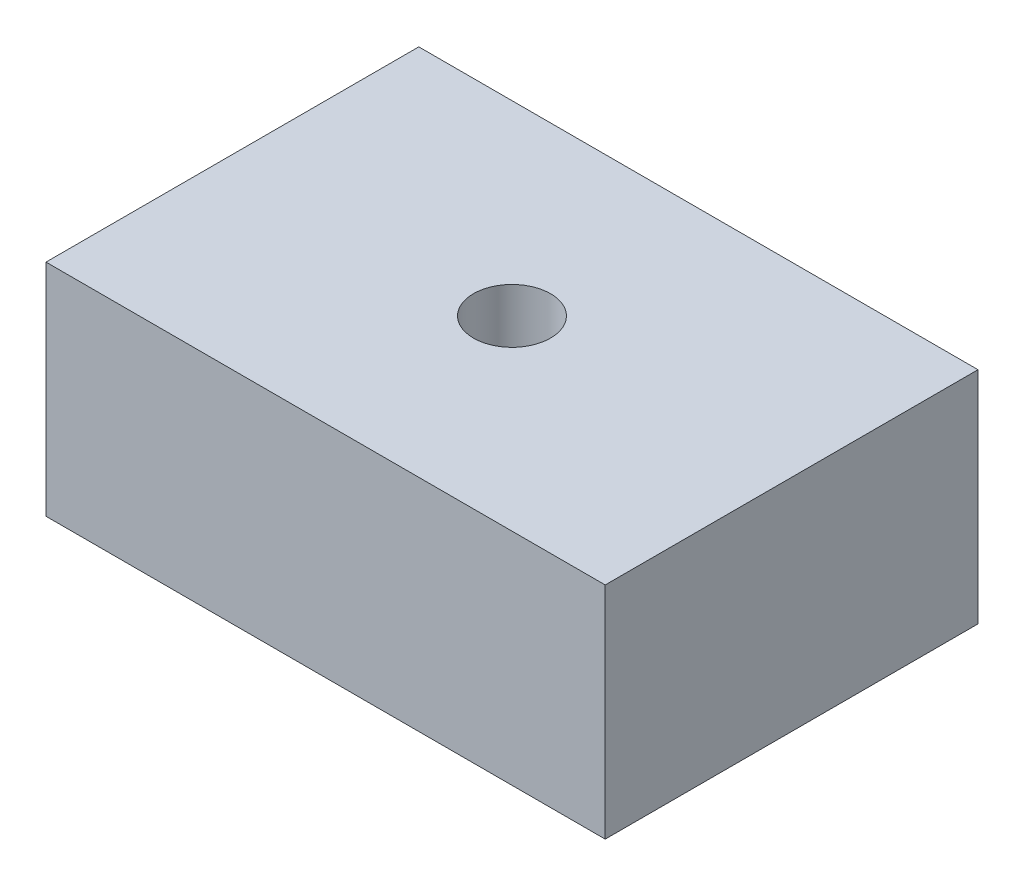
SolidWorks part; units mm, degrees
ref_plane "Front Plane" through (0, 0, 0) normal (0, 0, 1) x (1, 0, 0)
ref_plane "Top Plane" through (0, 0, 0) normal (0, 1, 0) x (1, 0, 0)
ref_plane "Right Plane" through (0, 0, 0) normal (1, 0, 0) x (0, 0, -1)
sketch "Sketch1" plane through (0, 0, 0) normal (0, 1, 0) x (1, 0, 0)
  line L1 (-38.1, 25.4) -> (38.1, 25.4)
  line L2 (-38.1, 25.4) -> (-38.1, -25.4)
  line L3 (-38.1, -25.4) -> (38.1, -25.4)
  line L4 (38.1, 25.4) -> (38.1, -25.4)
  line L5 (-38.1, 25.4) -> (38.1, -25.4) construction
  line L6 (-38.1, -25.4) -> (38.1, 25.4) construction
  circle A0 centre (0, 0) radius 5.25
  dimension "D1" = 50.8
  dimension "D2" = 76.2
extrude "Boss-Extrude1" add sketch "Sketch1" along normal blind 30
